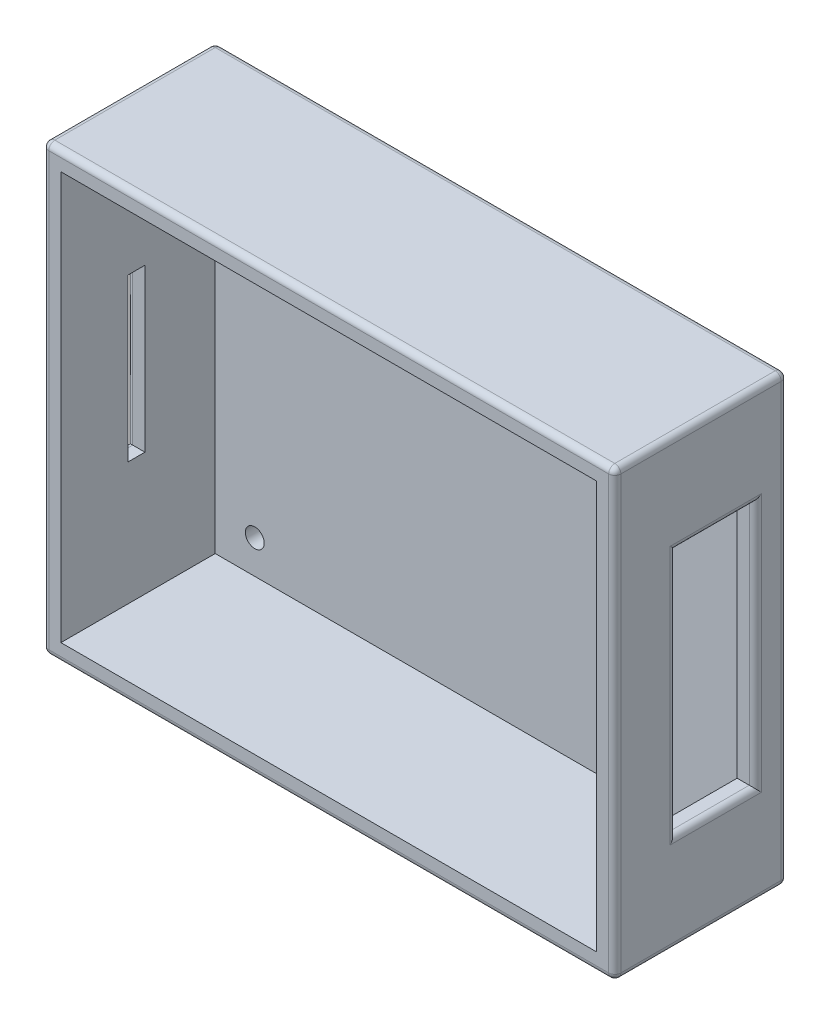
SolidWorks part; units mm, degrees
ref_plane "Спереди" through (0, 0, 0) normal (0, 0, 1) x (1, 0, 0)
ref_plane "Сверху" through (0, 0, 0) normal (0, 1, 0) x (1, 0, 0)
ref_plane "Справа" through (0, 0, 0) normal (1, 0, 0) x (0, 0, -1)
other "Configuration Table"
sketch "Эскиз1" plane through (0, 0, 0) normal (0, 0, 1) x (1, 0, 0)
  line L9 (-47.5, -8.4645) -> (46.5, -8.4645)
  line L10 (-47.5, -8.4645) -> (-47.5, -81.4645)
  line L11 (-47.5, -81.4645) -> (46.5, -81.4645)
  line L12 (46.5, -8.4645) -> (46.5, -81.4645)
  circle A0 centre (-38, -16.9645) radius 1.55
  circle A1 centre (38, -16.9645) radius 1.55
  circle A2 centre (38, -72.9645) radius 1.55
  circle A3 centre (-38, -72.9645) radius 1.55
  point P0 (0, 0)
  dimension "D3" = 8.5
  dimension "D1" = 73
  dimension "D2" = 8.5
  dimension "D4" = 94
  dimension "D5" = 76
  dimension "D6" = 56
extrude "Бобышка-Вытянуть2" add sketch "Эскиз1" along normal blind 28.35
sketch "Эскиз3" plane through (0, 0, 28.35) normal (0, 0, 1) x (1, 0, 0)
  line L0 (46.5, -8.4645) -> (-47.5, -8.4645) construction
  line L1 (-44.5, -11.4645) -> (43.5, -11.4645)
  line L2 (-44.5, -11.4645) -> (-44.5, -78.4645)
  line L3 (-44.5, -78.4645) -> (43.5, -78.4645)
  line L4 (43.5, -11.4645) -> (43.5, -78.4645)
  line L5 (-47.5, -8.4645) -> (-47.5, -81.4645) construction
  line L6 (-47.5, -81.4645) -> (46.5, -81.4645) construction
  line L7 (46.5, -81.4645) -> (46.5, -8.4645) construction
  dimension "D1" = 3
  dimension "D2" = 3
  dimension "D3" = 3
  dimension "D4" = 3
extrude "Вырез-Вытянуть1" cut sketch "Эскиз3" against normal blind 25.35
sketch "Эскиз4" plane through (46.5, 0, 0) normal (1, 0, 0) x (0, 0, -1)
  line L0 (-28.35, -81.4645) -> (-28.35, -8.4645) construction
  line L1 (-18.25, -24.8069) -> (-5.25, -24.8069)
  line L2 (-18.25, -24.8069) -> (-18.25, -65.3069)
  line L3 (-18.25, -65.3069) -> (-5.25, -65.3069)
  line L4 (-5.25, -24.8069) -> (-5.25, -65.3069)
  dimension "D1" = 40.5
  dimension "D2" = 13
  dimension "D3" = 23.1
extrude "Вырез-Вытянуть3" cut sketch "Эскиз4" against normal up to surface (3 mm away) up to face at (43.5, -44.9645, 15.675)
chamfer "Фаска1" distance 2 angle 45 1 edges at (43.5, -45.0569, 18.25)
sketch "Эскиз6" plane through (-47.5, 0, 0) normal (-1, 0, 0) x (0, 0, 1)
  line L0 (28.35, -8.4645) -> (28.35, -81.4645) construction
  line L1 (14.55, -31.6645) -> (17.35, -31.6645)
  line L2 (14.55, -31.6645) -> (14.55, -58.2645)
  line L3 (14.55, -58.2645) -> (17.35, -58.2645)
  line L4 (17.35, -31.6645) -> (17.35, -58.2645)
  line L5 (14.55, -31.6645) -> (17.35, -58.2645) construction
  line L6 (14.55, -58.2645) -> (17.35, -31.6645) construction
  point P0 (15.95, -44.9645)
  point P7 (28.35, -44.9645)
  dimension "D1" = 13.8
  dimension "D2" = 26.6
  dimension "D3" = 2.8
extrude "Вырез-Вытянуть4" cut sketch "Эскиз6" against normal up to surface (3 mm away) up to face at (-44.5, -44.9645, 15.675)
fillet "Скругление1" radius 1 20 edges at (46.5, -8.4645, 14.175) (46.5, -44.9645, 28.35) (-0.5, -8.4645, 28.35) (-47.5, -44.9645, 28.35) (-0.5, -81.4645, 28.35) (46.5, -24.8069, 11.75) (46.5, -45.0569, 18.25) (46.5, -65.3069, 11.75) (46.5, -45.0569, 5.25) (-0.5, -8.4645, 0) (46.5, -44.9645, 0) (46.5, -81.4645, 14.175) (-0.5, -81.4645, 0) (-47.5, -44.9645, 0) (-47.5, -81.4645, 14.175) (-47.5, -44.9645, 14.55) (-47.5, -44.9645, 17.35) (-47.5, -58.2645, 15.95) (-47.5, -31.6645, 15.95) (-47.5, -8.4645, 14.175)
sketch "Эскиз7" plane through (0, -81.4645, 0) normal (0, -1, 0) x (1, 0, 0)
  text T0 "SDrive" height in points 48
extrude "Бобышка-Вытянуть3" add sketch "Эскиз7" along normal blind 0.8
